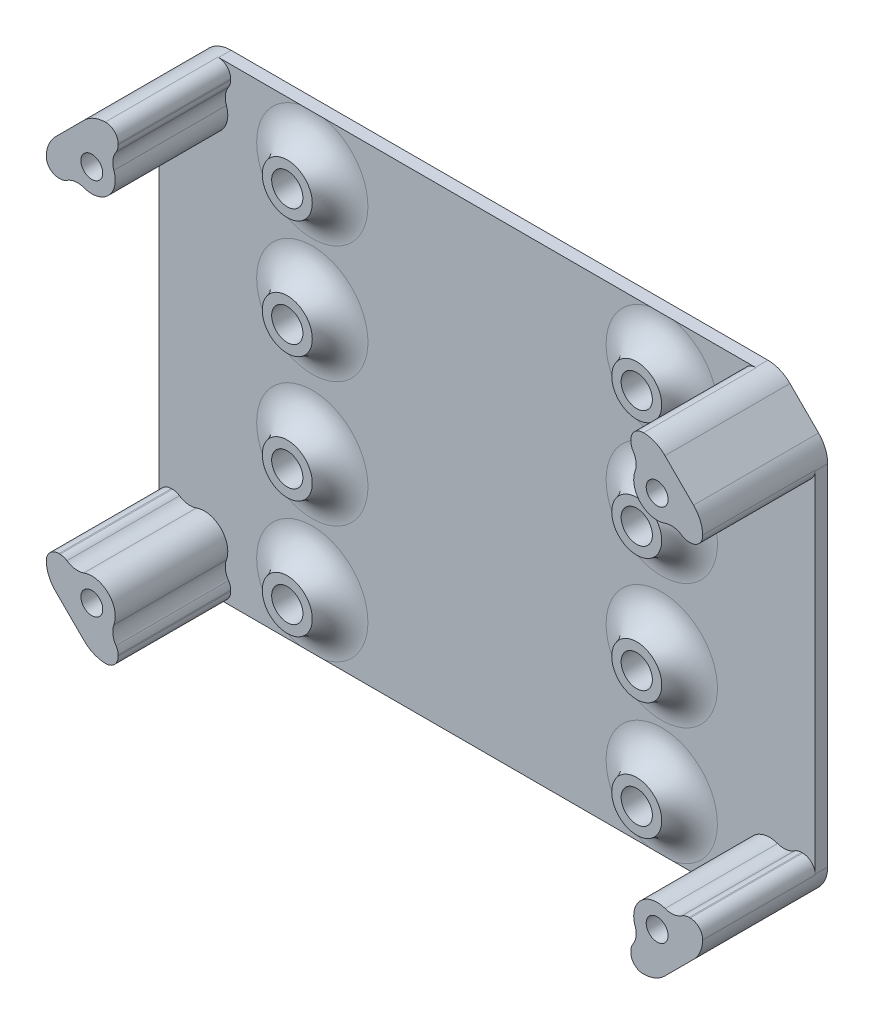
SolidWorks part; units mm, degrees
material "ABS"
ref_plane "Спереди" through (0, 0, 0) normal (0, 0, 1) x (1, 0, 0)
ref_plane "Сверху" through (0, 0, 0) normal (0, 1, 0) x (1, 0, 0)
ref_plane "Справа" through (0, 0, 0) normal (1, 0, 0) x (0, 0, -1)
sketch "Эскиз1" plane through (0, 0, 0) normal (0, 0, 1) x (1, 0, 0)
  line L0 (-52.5, 30) -> (-45, 37.5)
  line L1 (-45, 37.5) -> (45, 37.5)
  line L2 (-52.5, 30) -> (-52.5, -30)
  line L3 (-45, -37.5) -> (45, -37.5)
  line L4 (52.5, 30) -> (52.5, -30)
  line L5 (-52.5, 37.5) -> (52.5, -37.5) construction
  line L6 (-52.5, -37.5) -> (52.5, 37.5) construction
  line L7 (45, 37.5) -> (52.5, 30)
  line L8 (45, -37.5) -> (52.5, -30)
  line L9 (-52.5, -30) -> (-45, -37.5)
  point P0 (0, 0)
  dimension "D1" = 75
  dimension "D2" = 105
extrude "Бобышка-Вытянуть1" add sketch "Эскиз1" along normal blind 20
sketch "Эскиз2" plane through (0, 0, 20) normal (0, 0, 1) x (1, 0, 0)
  line L0 (-48.75, 33.75) -> (-38.4079, 23.4079) construction
  line L1 (-45, 37.5) -> (-52.5, 30) construction
  line L2 (-52.5, 0) -> (52.5, 0) construction
  line L3 (-52.5, 30) -> (-52.5, -30) construction
  line L4 (52.5, -30) -> (52.5, 30) construction
  line L5 (0, 37.5) -> (0, -37.5) construction
  line L6 (45, 37.5) -> (-45, 37.5) construction
  line L7 (-45, -37.5) -> (45, -37.5) construction
  line L8 (48.75, 33.75) -> (38.4079, 23.4079) construction
  line L9 (48.75, -33.75) -> (38.4079, -23.4079) construction
  line L10 (-48.75, -33.75) -> (-38.4079, -23.4079) construction
  circle A0 centre (-45.2145, 30.2145) radius 1.75
  circle A1 centre (45.2145, 30.2145) radius 1.75
  circle A2 centre (45.2145, -30.2145) radius 1.75
  circle A3 centre (-45.2145, -30.2145) radius 1.75
  dimension "D1" = 3.5
  dimension "D2" = 5
extrude "Вырез-Вытянуть1" cut sketch "Эскиз2" against normal blind 34
shell "Оболочка1" thickness 2
fillet "Скругление1" radius 10 8 edges at (-45.7448, -33.9268, 11) (-48.9268, -30.7448, 11) (48.9268, -30.7448, 11) (45.7448, -33.9268, 11) (45.7448, 33.9268, 11) (48.9268, 30.7448, 11) (-48.9268, 30.7448, 11) (-45.7448, 33.9268, 11)
fillet "Скругление2" radius 3 8 edges at (-50.5, 29.1716, 11) (-44.1716, 35.5, 11) (-44.1716, -35.5, 11) (-50.5, -29.1716, 11) (44.1716, -35.5, 11) (50.5, -29.1716, 11) (50.5, 29.1716, 11) (44.1716, 35.5, 11)
fillet "Скругление3" radius 5 8 edges at (-52.5, 30, 10) (-45, 37.5, 10) (45, 37.5, 10) (52.5, 30, 10) (52.5, -30, 10) (45, -37.5, 10) (-52.5, -30, 10) (-45, -37.5, 10)
ref_plane "Плоскость1" through (42.9289, -37.5, 20) normal (1, 0, 0) x (0, 0, -1)
sketch "Эскиз4" plane through (0, 0, 20) normal (0, 0, 1) x (1, 0, 0)
  line L1 (-41, 63.3728) -> (41, 63.3728)
  line L2 (-41, 63.3728) -> (-41, -63.3728)
  line L3 (-41, -63.3728) -> (41, -63.3728)
  line L4 (41, 63.3728) -> (41, -63.3728)
  line L5 (-41, 63.3728) -> (41, -63.3728) construction
  line L6 (-41, -63.3728) -> (41, 63.3728) construction
  point P0 (0, 0)
  dimension "D1" = 82
extrude "Вырез-Вытянуть2" cut sketch "Эскиз4" against normal up to surface (18 mm away) up to face at (0, 0, 2)
fillet "Скругление4" radius 2 8 edges at (41, -34.6057, 11) (41, -37.5, 11) (-41, -34.6057, 11) (-41, -37.5, 11) (-41, 34.6057, 11) (-41, 37.5, 11) (41, 34.6057, 11) (41, 37.5, 11)
sketch "Эскиз5" plane through (0, 0, 20) normal (0, 0, 1) x (1, 0, 0)
  line L1 (-86.9479, 26) -> (86.9479, 26)
  line L2 (-86.9479, 26) -> (-86.9479, -26)
  line L3 (-86.9479, -26) -> (86.9479, -26)
  line L4 (86.9479, 26) -> (86.9479, -26)
  line L5 (-86.9479, 26) -> (86.9479, -26) construction
  line L6 (-86.9479, -26) -> (86.9479, 26) construction
  point P0 (0, 0)
  dimension "D1" = 52
extrude "Вырез-Вытянуть3" cut sketch "Эскиз5" against normal up to surface (18 mm away)
fillet "Скругление5" radius 2 8 edges at (49.6057, -26, 11) (52.5, -26, 11) (49.6057, 26, 11) (52.5, 26, 11) (-49.6057, -26, 11) (-52.5, -26, 11) (-49.6057, 26, 11) (-52.5, 26, 11)
sketch "Эскиз6" plane through (0, 0, 2) normal (0, 0, 1) x (1, 0, 0)
  line L0 (-52.5, 0) -> (52.5, 0) construction
  line L1 (-52.5, -27.9289) -> (-52.5, 27.9289) construction
  line L2 (52.5, 27.9289) -> (52.5, -27.9289) construction
  line L3 (0, 37.5) -> (0, -37.5) construction
  line L4 (-42.9289, 37.5) -> (42.9289, 37.5) construction
  line L5 (42.9289, -37.5) -> (-42.9289, -37.5) construction
  line L6 (-27.95, -10) -> (27.95, -28.8) construction
  line L7 (-27.95, 28.8) -> (27.95, 28.8) construction
  line L8 (-27.95, 28.8) -> (-27.95, 10) construction
  line L9 (-27.95, 10) -> (27.95, 10) construction
  line L10 (27.95, 28.8) -> (27.95, 10) construction
  line L11 (-27.95, 28.8) -> (27.95, 10) construction
  line L12 (-27.95, 10) -> (27.95, 28.8) construction
  line L13 (-27.95, -28.8) -> (27.95, -10) construction
  line L14 (27.95, -28.8) -> (27.95, -10) construction
  line L15 (-27.95, -10) -> (27.95, -10) construction
  line L16 (-27.95, -28.8) -> (-27.95, -10) construction
  line L17 (-27.95, -28.8) -> (27.95, -28.8) construction
  circle A0 centre (-27.95, 28.8) radius 4
  circle A1 centre (27.95, 28.8) radius 4
  circle A2 centre (27.95, 10) radius 4
  circle A3 centre (-27.95, 10) radius 4
  circle A4 centre (-27.95, -10) radius 4
  circle A5 centre (27.95, -10) radius 4
  circle A6 centre (27.95, -28.8) radius 4
  circle A7 centre (-27.95, -28.8) radius 4
  point P12 (0, 19.4)
  point P29 (0, -19.4)
  dimension "D3" = 8
  dimension "D1" = 55.9
  dimension "D2" = 18.8
  dimension "D4" = 10
extrude "Бобышка-Вытянуть2" add sketch "Эскиз6" along normal blind 4
fillet "Скругление6" radius 5 8 edges at (-31.95, 28.8, 2) (23.95, 28.8, 2) (23.95, 10, 2) (-31.95, 10, 2) (-31.95, -10, 2) (23.95, -10, 2) (23.95, -28.8, 2) (-31.95, -28.8, 2)
sketch "Эскиз7" plane through (0, 0, 6) normal (0, 0, 1) x (1, 0, 0)
  circle A0 centre (-27.95, 28.8) radius 2.5
  circle A1 centre (27.95, 28.8) radius 2.5
  circle A2 centre (27.95, 10) radius 2.5
  circle A3 centre (-27.95, 10) radius 2.5
  circle A4 centre (-27.95, -10) radius 2.5
  circle A5 centre (27.95, -10) radius 2.5
  circle A6 centre (27.95, -28.8) radius 2.5
  circle A7 centre (-27.95, -28.8) radius 2.5
  dimension "D1" = 5
extrude "Вырез-Вытянуть4" cut sketch "Эскиз7" against normal blind 6
